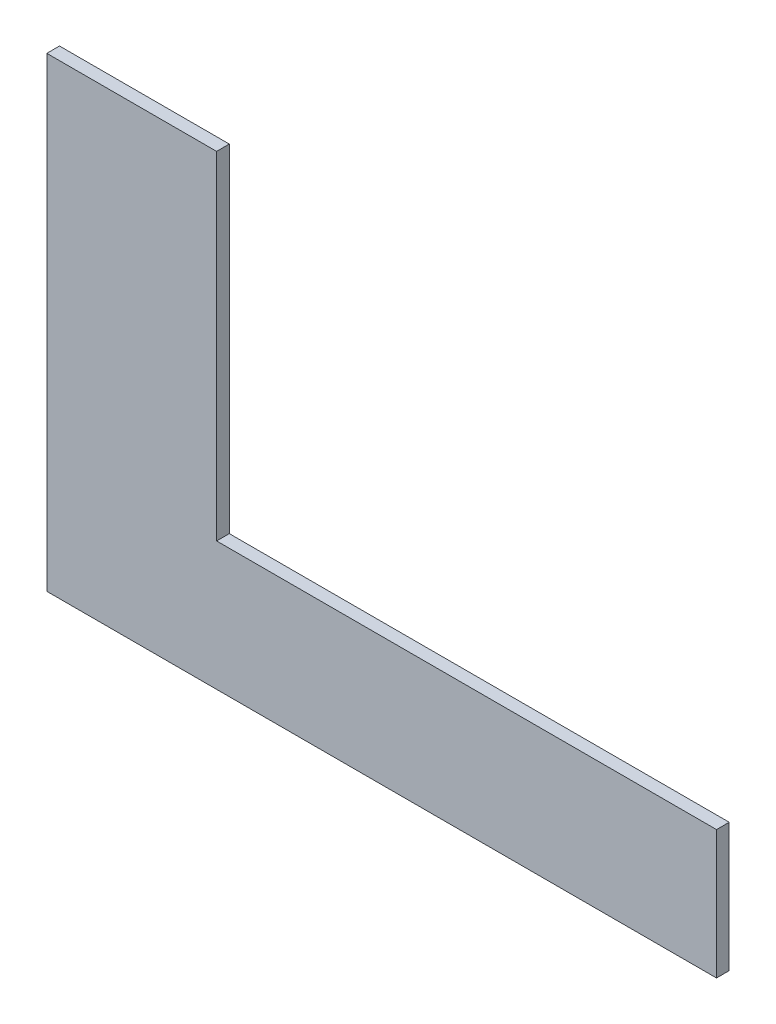
SolidWorks part; units mm, degrees
ref_plane "Ön Düzlem" through (0, 0, 0) normal (0, 0, 1) x (1, 0, 0)
ref_plane "Üst Düzlem" through (0, 0, 0) normal (0, 1, 0) x (1, 0, 0)
ref_plane "Sağ Düzlem" through (0, 0, 0) normal (1, 0, 0) x (0, 0, -1)
sketch "Çizim1" plane through (0, 0, 0) normal (0, 0, 1) x (1, 0, 0)
  line L0 (-517.2411, 843.5391) -> (-517.2411, -126.4609)
  line L1 (-517.2411, -126.4609) -> (1057.7589, -126.4609)
  line L2 (1057.7589, -126.4609) -> (1057.7589, -891.4609)
  line L3 (1057.7589, -891.4609) -> (-1052.2411, -891.4609)
  line L4 (-1052.2411, -891.4609) -> (-1052.2411, 843.5391)
  line L5 (-1052.2411, 843.5391) -> (-517.2411, 843.5391)
  dimension "D1" = 970
  dimension "D2" = 1575
  dimension "D3" = 765
  dimension "D4" = 2110
  dimension "D5" = 1735
base flange "Taban-Flanş1" sketch "Çizim1" thickness 40 reverse thickness direction no parameters "D1"=4
sketch "Çizim2" plane through (0, 0, 0) normal (0, 0, 1) x (1, 0, 0)
  line L0 (-517.2411, -126.4609) -> (-517.2411, 843.5391) construction
  line L1 (-1052.2411, 843.5391) -> (-517.2411, 843.5391)
  line L2 (-1052.2411, 843.5391) -> (-1052.2411, 578.5391)
  line L3 (-1052.2411, 578.5391) -> (-517.2411, 578.5391)
  line L4 (-517.2411, 843.5391) -> (-517.2411, 578.5391)
  line L6 (1057.7589, -891.4609) -> (1057.7589, -126.4609) construction
  dimension "D1" = 535
  dimension "D2" = 1575
  dimension "D3" = 705
extrude "Kes-Ekstrüzyon1" cut sketch "Çizim2" against normal through all both and the other way through all
sketch "Çizim3" plane through (0, 0, 0) normal (0, 0, 1) x (1, 0, 0)
  line L0 (1057.7589, -891.4609) -> (1057.7589, -126.4609) construction
  line L1 (-517.2411, -126.4609) -> (1057.7589, -126.4609)
  line L2 (-517.2411, -126.4609) -> (-517.2411, -486.4609)
  line L3 (-517.2411, -486.4609) -> (1057.7589, -486.4609)
  line L4 (1057.7589, -126.4609) -> (1057.7589, -486.4609)
  line L5 (-1052.2411, -891.4609) -> (1057.7589, -891.4609) construction
  dimension "D1" = 405
extrude "Kes-Ekstrüzyon2" cut sketch "Çizim3" against normal through all both and the other way through all
sketch "Çizim5" plane through (0, 0, 0) normal (0, 0, 1) x (1, 0, 0)
  line L0 (-517.2411, -486.4609) -> (-517.2411, 578.5391) construction
  line L1 (-1052.2411, 578.5391) -> (-517.2411, 578.5391)
  line L2 (-1052.2411, 578.5391) -> (-1052.2411, 576.5391)
  line L3 (-1052.2411, 576.5391) -> (-517.2411, 576.5391)
  line L4 (-517.2411, 578.5391) -> (-517.2411, 576.5391)
  line L5 (-1052.2411, -891.4609) -> (1057.7589, -891.4609) construction
  dimension "D1" = 1468
extrude "Kes-Ekstrüzyon3" cut sketch "Çizim5" against normal through all both and the other way through all
sketch "Çizim6" plane through (0, 0, 0) normal (0, 0, 1) x (1, 0, 0)
  line L6 (-517.2411, -486.4609) -> (-517.2411, 576.5391)
  line L7 (-517.2411, 576.5391) -> (-1052.2411, 576.5391)
  line L8 (-1052.2411, 576.5391) -> (-1052.2411, -891.4609)
  line L9 (-1052.2411, -891.4609) -> (1057.7589, -891.4609)
  line L10 (1057.7589, -891.4609) -> (1057.7589, -486.4609)
  line L11 (1057.7589, -486.4609) -> (-517.2411, -486.4609)
  line L12 (-517.2411, -486.4609) -> (-517.2411, 576.5391)
  line L13 (-517.2411, 576.5391) -> (-1052.2411, 576.5391)
  line L14 (-1052.2411, 576.5391) -> (-1052.2411, -891.4609)
  line L15 (-1052.2411, -891.4609) -> (1057.7589, -891.4609)
  line L16 (1057.7589, -891.4609) -> (1057.7589, -486.4609)
  line L17 (1057.7589, -486.4609) -> (-517.2411, -486.4609)
  dimension "D2" = 1575
  dimension "D3" = 1063
  dimension "D4" = 535
  dimension "D5" = 1468
  dimension "D6" = 2110
  dimension "D7" = 405
  dimension "D1" = 0
sketch "Büküm-Çizgileri1" [suppressed] plane through (0, 0, 0) normal (0, 1, 0) x (1, 0, 0)
sketch "Sınırlandırma-Kutusu1" [suppressed] plane through (0, 0, 0) normal (0, 1, 0) x (1, 0, 0)
sheet metal parameters "Sac-Levha1" thickness 40 parameters "D1"=4
flat pattern "Düz-Çoğaltma1" [suppressed]
sketch "Büküm-Çizgileri2" plane through (0, 0, 0) normal (0, 1, 0) x (1, 0, 0)
sketch3d "Sınırlandırma-Kutusu2" [suppressed]
  line L0 (-1052.2411, -891.4609, 0) -> (1057.7589, -891.4609, 0) construction
  line L1 (-1052.2411, 843.5391, 0) -> (1057.7589, 843.5391, 0) construction
  line L2 (-1052.2411, -891.4609, 0) -> (-1052.2411, 843.5391, 0) construction
  line L3 (1057.7589, -891.4609, 0) -> (1057.7589, 843.5391, 0) construction
sheet metal parameters "Sac-Levha2" thickness 40 parameters "D1"=4
flat pattern "Düz-Çoğaltma1"
sketch "Büküm-Çizgileri2" plane through (0, 0, 0) normal (0, 1, 0) x (1, 0, 0)
sketch3d "Sınırlandırma-Kutusu2" [suppressed]
  line L0 (-1052.2411, -891.4609, 0) -> (1057.7589, -891.4609, 0) construction
  line L1 (-1052.2411, 578.5391, 0) -> (1057.7589, 578.5391, 0) construction
  line L2 (-1052.2411, -891.4609, 0) -> (-1052.2411, 578.5391, 0) construction
  line L3 (1057.7589, -891.4609, 0) -> (1057.7589, 578.5391, 0) construction
sheet metal parameters "Sac-Levha3" thickness 40 parameters "D1"=4
flat pattern "Düz-Çoğaltma1"
sketch "Büküm-Çizgileri2" plane through (0, 0, 0) normal (0, 1, 0) x (1, 0, 0)
sketch3d "Sınırlandırma-Kutusu2" [suppressed]
  line L0 (-1052.2411, -891.4609, 0) -> (1057.7589, -891.4609, 0) construction
  line L1 (-1052.2411, 578.5391, 0) -> (1057.7589, 578.5391, 0) construction
  line L2 (-1052.2411, -891.4609, 0) -> (-1052.2411, 578.5391, 0) construction
  line L3 (1057.7589, -891.4609, 0) -> (1057.7589, 578.5391, 0) construction
sheet metal parameters "Sac-Levha4" thickness 40 parameters "D1"=4
flat pattern "Düz-Çoğaltma1"
sketch "Büküm-Çizgileri2" plane through (0, 0, 0) normal (0, 1, 0) x (1, 0, 0)
sketch3d "Sınırlandırma-Kutusu2" [suppressed]
  line L0 (-1052.2411, -891.4609, 0) -> (1057.7589, -891.4609, 0) construction
  line L1 (-1052.2411, 576.5391, 0) -> (1057.7589, 576.5391, 0) construction
  line L2 (-1052.2411, -891.4609, 0) -> (-1052.2411, 576.5391, 0) construction
  line L3 (1057.7589, -891.4609, 0) -> (1057.7589, 576.5391, 0) construction
